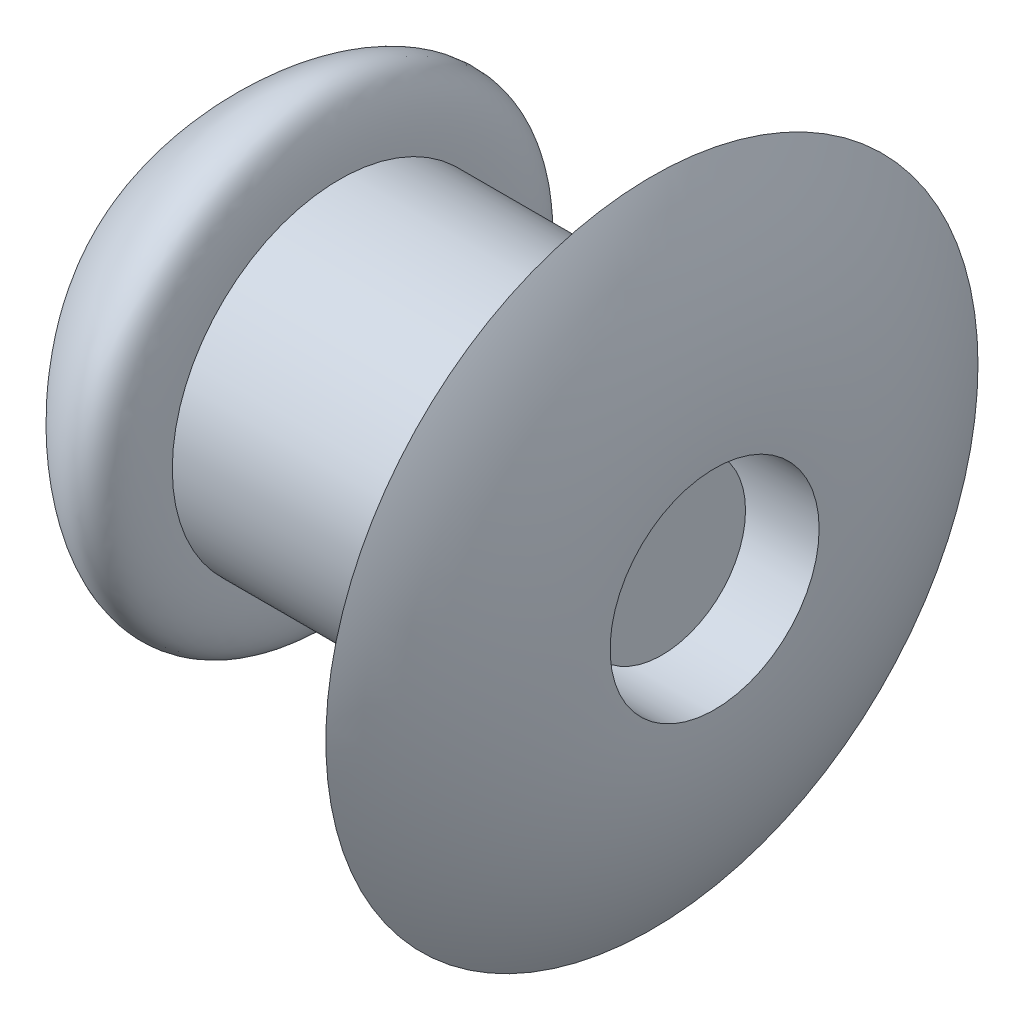
SolidWorks part; units mm, degrees
material "AISI 316 Arkusz stali nierdzewnej (SS)"
ref_plane "Płaszczyzna przednia" through (0, 0, 0) normal (0, 0, 1) x (1, 0, 0)
ref_plane "Płaszczyzna górna" through (0, 0, 0) normal (0, 1, 0) x (1, 0, 0)
ref_plane "Płaszczyzna prawa" through (0, 0, 0) normal (1, 0, 0) x (0, 0, -1)
sketch "Szkic1" plane through (0, 0, 0) normal (0, 0, 1) x (1, 0, 0)
  line L0 (350.8561, 893.6816) -> (345.4445, 893.6816)
  line L1 (351.4866, 894.9316) -> (347, 894.9316)
  line L2 (347, 894.9316) -> (347, 894.6816)
  line L3 (347, 894.6816) -> (350.8561, 894.6816)
  line L4 (350.8561, 894.6816) -> (350.8561, 893.6816)
  line L5 (350.7366, 897.5816) -> (350.7366, 895.6816)
  line L6 (350.7366, 895.6816) -> (347, 895.6816)
  line L7 (350.8561, 893.6816) -> (345.4445, 893.6816) construction
  line L8 (350.8561, 893.6816) -> (345.4445, 893.6816) construction
  line L9 (351.4866, 893.6816) -> (350.8561, 893.6816) construction
  line L10 (350.7366, 521.1816) -> (350.7366, 901.1816) construction
  line L11 (347, 4.3583) -> (347, 898.0048) construction
  arc A0 (351.4866, 894.9316) -> (350.7366, 897.5816) centre (346.4299, 894.9316) ccw
  spline S0 degree 3 poles (347, 895.6816) (347.0366, 898.0214) (343.5366, 893.3094) (345.7587, 895.1701) (346.0554, 894.8565) knots 0 0 0 0 0.744502 1 1 1 1
  spline S1 degree 2 poles (346.0554, 894.8565) (345.1724, 894.8746) (345.4445, 893.6816) knots 0 0 0 1 1 1
  point P25 (0, 0)
  point P26 (350.9526, 893.6816)
  dimension "D18" = 4.8231
  dimension "D1" = 2
  dimension "D2" = 0.1195
  dimension "D3" = 4
  dimension "D4" = 2.5
  dimension "D5" = 0.75
  dimension "D6" = 7.8
  dimension "D7" = 0.9668
  dimension "D8" = 1.1117
  dimension "D9" = 1.175
  dimension "D10" = 1.2811
  dimension "D11" = 2.7999
  dimension "D12" = 0.4548
  dimension "D13" = 0.9446
  dimension "D14" = 1.1893
  dimension "D15" = 1.3067
  dimension "D16" = 2.0033
  dimension "D17" = 1.5555
revolve "Obrót1" add sketch "Szkic1" angle 360 about L7
